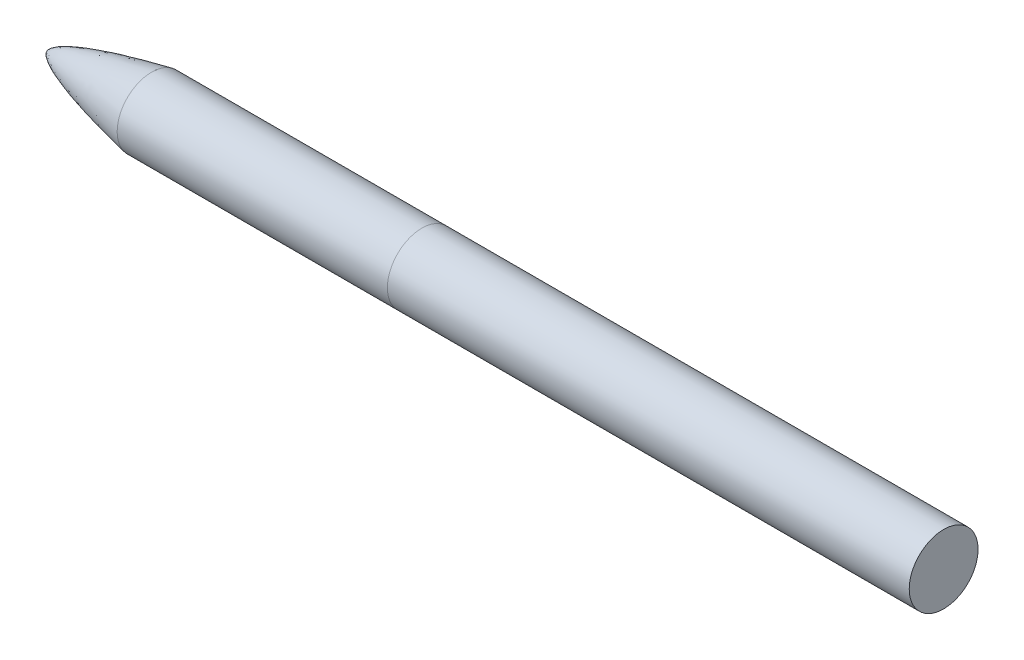
SolidWorks part; units mm, degrees
ref_plane "Front Plane" through (0, 0, 0) normal (0, 0, 1) x (1, 0, 0)
ref_plane "Top Plane" through (0, 0, 0) normal (0, 1, 0) x (1, 0, 0)
ref_plane "Right Plane" through (0, 0, 0) normal (1, 0, 0) x (0, 0, -1)
sketch "Sketch1" plane through (0, 0, 0) normal (0, 0, 1) x (1, 0, 0)
  line L1 (-35326.359, 4500) -> (0, 4500)
  line L3 (-35326.359, 0) -> (0, 0)
  line L4 (0, 4500) -> (0, 0)
  line L5 (-48976.359, 0) -> (-35326.359, 0)
  line L6 (0, 0) -> (68222.6898, 0)
  line L7 (0, 0) -> (0, 4500)
  line L8 (0, 4500) -> (68222.6898, 4500)
  line L9 (68222.6898, 0) -> (68222.6898, 4500)
  spline S0 degree 4 poles (-48976.359, 0) (-48976.3536, 0.5926) (-48976.3339, 1.7775) (-48976.277, 3.554) (-48976.1514, 5.9208) (-48975.9884, 8.2852) (-48975.7921, 10.647) (-48975.5077, 13.5958) (-48974.9758, 18.3059) (-48974.0754, 24.7619) (-48972.812, 32.0697) (-48971.2674, 39.6341) (-48969.4061, 47.7535) (-48966.8269, 57.8338) (-48963.0673, 70.656) (-48958.3805, 84.4984) (-48953.2836, 97.9382) (-48948.4576, 109.6529) (-48944.0575, 119.6982) (-48937.678, 133.4739) (-48929.0051, 150.825) (-48916.7053, 173.3455) (-48900.1791, 200.6549) (-48873.4136, 240.921) (-48829.808, 298.4887) (-48773.8331, 361.8976) (-48705.0882, 430.1311) (-48627.567, 499.6265) (-48547.2602, 565.689) (-48447.5933, 641.2892) (-48327.6167, 724.844) (-48177.5706, 821.3769) (-47996.2225, 928.5258) (-47813.1604, 1028.3664) (-47629.3641, 1122.2529) (-47427.7592, 1220.2267) (-47218.3887, 1316.8762) (-46980.5837, 1420.9762) (-46650.0309, 1558.1587) (-46262.6491, 1709.4723) (-45807.0257, 1876.2847) (-45282.5136, 2056.162) (-44755.0328, 2227.1066) (-44291.397, 2370.0555) (-43892.7664, 2488.501) (-43559.8544, 2584.7403) (-43293.128, 2660.3451) (-42959.2623, 2753.2207) (-42557.9459, 2862.2127) (-42088.8607, 2986.0794) (-41551.7077, 3123.5768) (-41080.8855, 3240.6609) (-40676.8079, 3338.9151) (-40339.76, 3419.4775) (-40069.9418, 3483.1701) (-39799.9529, 3546.1353) (-39529.802, 3608.4012) (-39259.4968, 3669.994) (-38955.2382, 3738.5565) (-38684.6226, 3798.7713) (-38447.7182, 3850.9359) (-38244.5783, 3895.287) (-38109.1206, 3924.7122) (-37973.6327, 3953.9976) (-37838.1152, 3983.1455) (-37702.5686, 4012.1581) (-37566.9936, 4041.0375) (-37431.3907, 4069.7859) (-37295.7606, 4098.4053) (-37160.1036, 4126.8977) (-37024.4207, 4155.265) (-36888.7115, 4183.5092) (-36752.9782, 4211.6319) (-36617.2184, 4239.6354) (-36481.4372, 4267.5205) (-36345.6275, 4295.2904) (-36226.7811, 4319.4875) (-36124.8864, 4340.1598) (-36039.9839, 4357.3363) (-35972.022, 4371.0567) (-35904.1239, 4384.7358) (-35836.0974, 4398.4119) (-35768.2734, 4412.0197) (-35700.0977, 4425.6691) (-35632.4912, 4439.178) (-35563.9192, 4452.8504) (-35496.9918, 4466.1699) (-35435.7412, 4478.3326) (-35387.6042, 4487.8777) (-35337.8568, 4497.7267) (-35307.3717, 4503.7561) (-35259.4967, 4513.2159) (-35221.5364, 4520.7035) (-35176.1014, 4529.6593) (-35135.1603, 4537.7157) (-35091.5033, 4546.299) (-35049.4759, 4554.5498) (-35006.4818, 4562.9814) (-34964.0297, 4571.2957) (-34910.626, 4581.7428) (-34846.7184, 4594.224) (-34772.0432, 4608.7792) (-34686.7606, 4625.3618) (-34601.4339, 4641.9135) (-34516.1213, 4658.4232) (-34430.7885, 4674.8979) (-34345.4564, 4691.3338) (-34260.1123, 4707.7337) (-34174.7643, 4724.0964) (-34089.4072, 4740.4231) (-34025.3856, 4752.6408) (-33982.7013, 4760.7742) (-33961.359, 4764.8378) knots 0 0 0 0 0 0.000148 0.000297 0.000445 0.000593 0.000742 0.00089 0.001187 0.00178 0.002373 0.002746 0.003119 0.003865 0.004978 0.00609 0.006777 0.007463 0.008149 0.008836 0.010577 0.012319 0.014572 0.016825 0.022678 0.030384 0.035722 0.04106 0.048735 0.05641 0.067032 0.077654 0.093392 0.109131 0.119225 0.129319 0.149507 0.166858 0.18421 0.218913 0.253616 0.288319 0.323022 0.357725 0.375077 0.392428 0.40978 0.427131 0.461834 0.496537 0.53124 0.565943 0.583295 0.600646 0.617998 0.635349 0.652701 0.670052 0.687404 0.713431 0.722107 0.730783 0.739459 0.748134 0.75681 0.765486 0.774162 0.782837 0.791513 0.800189 0.808865 0.81754 0.826216 0.834892 0.843568 0.852244 0.860919 0.865257 0.869595 0.873933 0.878271 0.882609 0.886947 0.891284 0.895622 0.89996 0.904298 0.908636 0.910805 0.912974 0.915693 0.918413 0.921133 0.923852 0.926572 0.929291 0.932011 0.93473 0.93745 0.94017 0.945609 0.951048 0.956487 0.961926 0.967365 0.972804 0.978243 0.983683 0.989122 0.994561 1 1 1 1 1 construction
  spline S3 degree 4 poles (-48976.359, 0) (-48976.3536, 0.5926) (-48976.3339, 1.7775) (-48976.277, 3.554) (-48976.1514, 5.9208) (-48975.9884, 8.2852) (-48975.7921, 10.647) (-48975.5077, 13.5958) (-48974.9758, 18.3059) (-48974.0754, 24.7619) (-48972.812, 32.0697) (-48971.2674, 39.6341) (-48969.4061, 47.7535) (-48966.8269, 57.8338) (-48963.0673, 70.656) (-48958.3805, 84.4984) (-48953.2836, 97.9382) (-48948.4576, 109.6529) (-48944.0575, 119.6982) (-48937.678, 133.4739) (-48929.0051, 150.825) (-48916.7053, 173.3455) (-48900.1791, 200.6549) (-48873.4136, 240.921) (-48829.808, 298.4887) (-48773.8331, 361.8976) (-48705.0882, 430.1311) (-48627.567, 499.6265) (-48547.2602, 565.689) (-48447.5933, 641.2892) (-48327.6167, 724.844) (-48177.5706, 821.3769) (-47996.2225, 928.5258) (-47813.1604, 1028.3664) (-47629.3641, 1122.2529) (-47427.7592, 1220.2267) (-47218.3887, 1316.8762) (-46980.5837, 1420.9762) (-46650.0309, 1558.1587) (-46262.6491, 1709.4723) (-45807.0257, 1876.2847) (-45282.5136, 2056.162) (-44755.0328, 2227.1066) (-44291.397, 2370.0555) (-43892.7664, 2488.501) (-43559.8544, 2584.7403) (-43293.128, 2660.3451) (-42959.2623, 2753.2207) (-42557.9459, 2862.2127) (-42088.8607, 2986.0794) (-41551.7077, 3123.5768) (-41080.8855, 3240.6609) (-40676.8079, 3338.9151) (-40339.76, 3419.4775) (-40069.9418, 3483.1701) (-39799.9529, 3546.1353) (-39529.802, 3608.4012) (-39259.4968, 3669.994) (-38955.2382, 3738.5565) (-38684.6226, 3798.7713) (-38447.7182, 3850.9359) (-38244.5783, 3895.287) (-38109.1206, 3924.7122) (-37973.6327, 3953.9976) (-37838.1152, 3983.1455) (-37702.5686, 4012.1581) (-37566.9936, 4041.0375) (-37431.3907, 4069.7859) (-37295.7606, 4098.4053) (-37160.1036, 4126.8977) (-37024.4207, 4155.265) (-36888.7115, 4183.5092) (-36752.9782, 4211.6319) (-36617.2184, 4239.6354) (-36481.4372, 4267.5205) (-36345.6275, 4295.2904) (-36226.7811, 4319.4875) (-36124.8864, 4340.1598) (-36039.9839, 4357.3363) (-35972.022, 4371.0567) (-35904.1239, 4384.7358) (-35836.0974, 4398.4119) (-35768.2734, 4412.0197) (-35700.0977, 4425.6691) (-35632.4912, 4439.178) (-35563.9192, 4452.8504) (-35496.9918, 4466.1699) (-35435.7412, 4478.3326) (-35387.6042, 4487.8777) (-35349.7294, 4495.3762) (-35334.1183, 4498.4652) (-35326.359, 4500) knots 0 0 0 0 0 0.000148 0.000297 0.000445 0.000593 0.000742 0.00089 0.001187 0.00178 0.002373 0.002746 0.003119 0.003865 0.004978 0.00609 0.006777 0.007463 0.008149 0.008836 0.010577 0.012319 0.014572 0.016825 0.022678 0.030384 0.035722 0.04106 0.048735 0.05641 0.067032 0.077654 0.093392 0.109131 0.119225 0.129319 0.149507 0.166858 0.18421 0.218913 0.253616 0.288319 0.323022 0.357725 0.375077 0.392428 0.40978 0.427131 0.461834 0.496537 0.53124 0.565943 0.583295 0.600646 0.617998 0.635349 0.652701 0.670052 0.687404 0.713431 0.722107 0.730783 0.739459 0.748134 0.75681 0.765486 0.774162 0.782837 0.791513 0.800189 0.808865 0.81754 0.826216 0.834892 0.843568 0.852244 0.860919 0.865257 0.869595 0.873933 0.878271 0.882609 0.886947 0.891284 0.895622 0.89996 0.904298 0.908636 0.910805 0.912974 0.912974 0.912974 0.912974 0.912974
  dimension "D2" = 35326.359
  dimension "D1" = 4500
  dimension "D3" = 68222.6898
revolve "Revolve1" add sketch "Sketch1" angle 360 about L3 region at (-22120.2891, 2130.6351, 0)
revolve "Revolve2" add sketch "Sketch1<3>" angle 360 about L6 region at (34111.3449, 2250, 0)
sketch "Sketch1<3>" plane through (0, 0, 0) normal (0, 0, 1) x (1, 0, 0) same geometry as "Sketch1"
equation "\"D\"=9"
equation "\"SS.H_Cone\"= 13.65"
equation "\"R\"= \"D\" / 2"
equation "\"SS.H_Fuse\" = 35.326359"
equation "\"n\"= 0.6"
equation "\"SH.H_Fuse\"= 68.222689847986"
equation "\"D2@Sketch1\"=\"SS.H_Fuse\""
equation "\"D3@Sketch1\"=\"SH.H_Fuse\""
equation "\"D1@Sketch1\"=\"R\""
